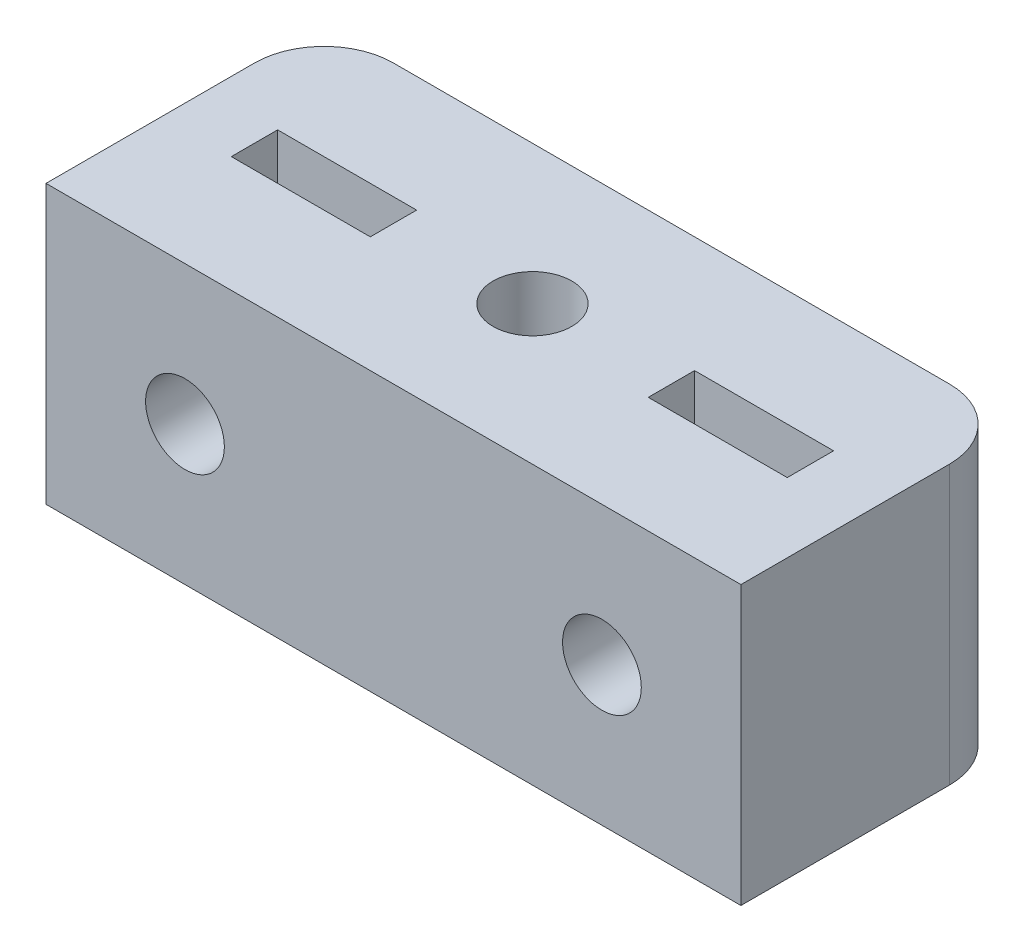
SolidWorks part; units mm, degrees
ref_plane "Front Plane" through (0, 0, 0) normal (0, 0, 1) x (1, 0, 0)
ref_plane "Top Plane" through (0, 0, 0) normal (0, 1, 0) x (1, 0, 0)
ref_plane "Right Plane" through (0, 0, 0) normal (1, 0, 0) x (0, 0, -1)
sketch "Sketch1" plane through (0, 0, 0) normal (0, 1, 0) x (1, 0, 0)
  line L1 (-15, -6) -> (15, -6)
  line L2 (-15, -6) -> (-15, 6)
  line L3 (-15, 6) -> (15, 6)
  line L4 (15, -6) -> (15, 6)
  line L5 (-15, -6) -> (15, 6) construction
  line L6 (-15, 6) -> (15, -6) construction
  point P0 (0, 0)
  dimension "D1" = 12
  dimension "D2" = 30
extrude "Boss-Extrude1" add sketch "Sketch1" along normal mid plane 12
sketch "Sketch2" plane through (0, 0, 6) normal (0, 0, 1) x (1, 0, 0)
  line L0 (-9, 6) -> (-9, -6) construction
  line L1 (-15, 6) -> (15, 6) construction
  line L3 (-15, 6) -> (-15, -6) construction
  line L4 (-15, -6) -> (15, -6) construction
  circle A0 centre (-9, 0) radius 1.7
  dimension "D2" = 3.4
  dimension "D1" = 6
extrude "Cut-Extrude1" cut sketch "Sketch2" against normal through all
sketch "Sketch3" plane through (0, 0, 0) normal (0, 0, 1) x (1, 0, 0)
  line L0 (-12, 3) -> (-12, 6)
  line L1 (-12, -3) -> (-6, -3)
  line L2 (-12, -3) -> (-12, 3)
  line L3 (-12, 3) -> (-6, 3) construction
  line L4 (-6, -3) -> (-6, 3)
  line L5 (-12, -3) -> (-6, 3) construction
  line L6 (-12, 3) -> (-6, -3) construction
  line L7 (-15, 6) -> (15, 6) construction
  line L8 (-12, 6) -> (-6, 6)
  line L9 (-6, 6) -> (-6, 3)
  circle A0 centre (-9, 0) radius 1.7 construction
  point P0 (-9, 0)
  dimension "D1" = 6
  dimension "D2" = 6
extrude "Cut-Extrude2" cut sketch "Sketch3" against normal mid plane 2
mirror "Mirror1" about plane through (0, 0, 0) normal (1, 0, 0) of "Cut-Extrude2", "Cut-Extrude1"
sketch "Sketch4" plane through (0, 6, 0) normal (0, 1, 0) x (1, 0, 0)
  circle A0 centre (0, 0) radius 1.7
  dimension "D1" = 3.4
extrude "Cut-Extrude3" cut sketch "Sketch4" against normal through all
sketch "Sketch5" plane through (0, 0, 0) normal (0, 1, 0) x (1, 0, 0)
  line L0 (-3, 3) -> (-3, 6)
  line L1 (-3, -3) -> (3, -3)
  line L2 (-3, -3) -> (-3, 3)
  line L3 (-3, 3) -> (3, 3) construction
  line L4 (3, -3) -> (3, 3)
  line L5 (-3, -3) -> (3, 3) construction
  line L6 (-3, 3) -> (3, -3) construction
  line L7 (15, 6) -> (-15, 6) construction
  line L8 (-3, 6) -> (3, 6)
  line L9 (3, 6) -> (3, 3)
  point P1 (0, 0)
  dimension "D1" = 6
  dimension "D2" = 6
extrude "Cut-Extrude4" cut sketch "Sketch5" against normal mid plane 2
fillet "Fillet1" radius 3 2 edges at (-15, 0, -6) (15, 0, -6)
equation "\"M3_d\"= 3.4"
equation "\"M3_nut_m\" = 2"
equation "\"M3_nut_s\" = 6"
equation "\"t\"= 3"
equation "\"D1@Sketch1\"=\"M3_nut_s\" + 2 * \"t\""
equation "\"D2@Sketch1\"=3 * \"M3_nut_s\" + 2 * \"t\" + 2 * \"t\""
equation "\"D1@Boss-Extrude1\"=\"M3_nut_s\" + 2 * \"t\""
equation "\"D1@Sketch2\"=\"t\" + \"M3_nut_s\" / 2 "
equation "\"D2@Sketch2\"=\"M3_d\""
equation "\"D1@Sketch3\"=\"M3_nut_s\""
equation "\"D2@Sketch3\"=\"M3_nut_s\""
equation "\"D1@Cut-Extrude2\"=\"M3_nut_m\""
equation "\"D1@Sketch4\"=\"M3_d\""
equation "\"D1@Sketch5\"=\"M3_nut_s\""
equation "\"D2@Sketch5\"=\"M3_nut_s\""
equation "\"D1@Cut-Extrude4\"=\"M3_nut_m\""
equation "\"D1@Fillet1\"=\"t\""
